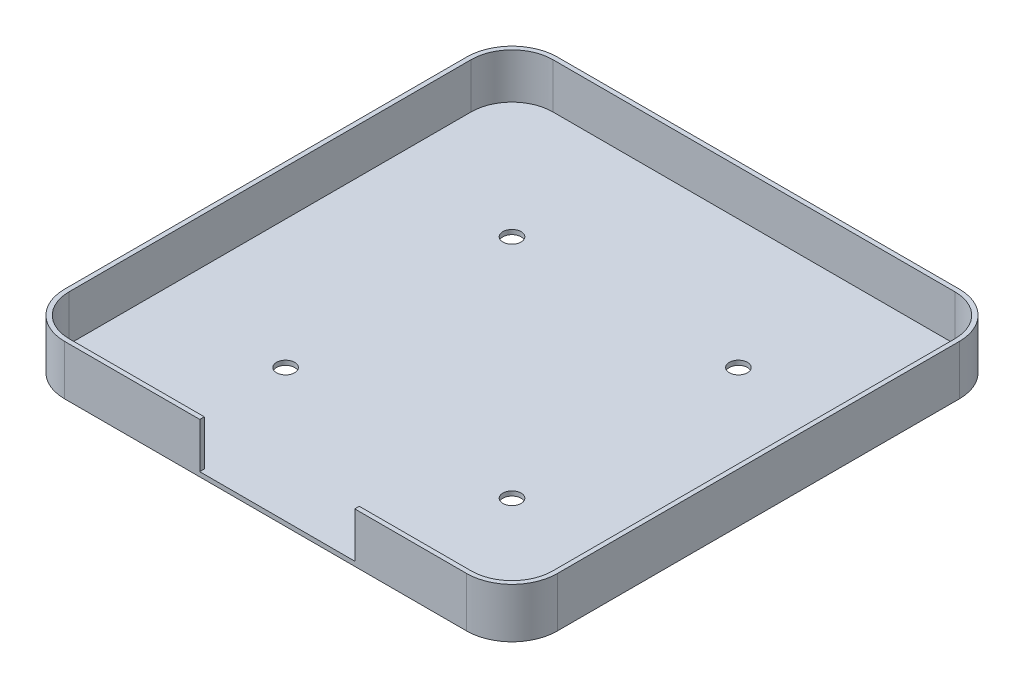
SolidWorks part; units mm, degrees
ref_plane "Front Plane" through (0, 0, 0) normal (0, 0, 1) x (1, 0, 0)
ref_plane "Top Plane" through (0, 0, 0) normal (0, 1, 0) x (1, 0, 0)
ref_plane "Right Plane" through (0, 0, 0) normal (1, 0, 0) x (0, 0, -1)
sketch "Sketch1" plane through (0, 0, 0) normal (0, 1, 0) x (1, 0, 0)
  line L0 (0, 0) -> (29, 0) construction
  line L1 (-25, -29) -> (25, -29)
  line L2 (-29, -25) -> (-29, 25)
  line L3 (-25, 29) -> (25, 29)
  line L4 (29, -25) -> (29, 25)
  line L5 (-29, -29) -> (29, 29) construction
  line L6 (-29, 29) -> (29, -29) construction
  line L7 (-53.4, -44.4) -> (-53.4, 44.4)
  line L8 (-44.4, -54.4) -> (44.4, -54.4)
  line L9 (-54.4, -44.4) -> (-54.4, 44.4)
  line L10 (-44.4, 54.4) -> (44.4, 54.4)
  line L11 (54.4, -44.4) -> (54.4, 44.4)
  line L12 (-54.4, -54.4) -> (54.4, 54.4) construction
  line L13 (-54.4, 54.4) -> (54.4, -54.4) construction
  line L14 (-44.4, 53.4) -> (44.4, 53.4)
  line L15 (53.4, -44.4) -> (53.4, 44.4)
  line L16 (-44.4, -53.4) -> (44.4, -53.4)
  arc A0 (-25, -29) -> (-29, -25) centre (-25, -25) cw
  arc A1 (25, -29) -> (29, -25) centre (25, -25) ccw
  arc A2 (25, 29) -> (29, 25) centre (25, 25) cw
  arc A3 (-29, 25) -> (-25, 29) centre (-25, 25) cw
  circle A4 centre (-25, 25) radius 2
  circle A5 centre (25, 25) radius 2
  circle A6 centre (25, -25) radius 2
  circle A7 centre (-25, -25) radius 2
  arc A8 (44.4, 54.4) -> (54.4, 44.4) centre (44.4, 44.4) cw
  arc A9 (44.4, -54.4) -> (54.4, -44.4) centre (44.4, -44.4) ccw
  arc A10 (-44.4, -54.4) -> (-54.4, -44.4) centre (-44.4, -44.4) cw
  arc A11 (-54.4, 44.4) -> (-44.4, 54.4) centre (-44.4, 44.4) cw
  arc A12 (-53.4, 44.4) -> (-44.4, 53.4) centre (-44.4, 44.4) cw
  arc A13 (44.4, 53.4) -> (53.4, 44.4) centre (44.4, 44.4) cw
  arc A14 (44.4, -53.4) -> (53.4, -44.4) centre (44.4, -44.4) ccw
  arc A15 (-44.4, -53.4) -> (-53.4, -44.4) centre (-44.4, -44.4) cw
  point P0 (0, 0)
  dimension "D3" = 4
  dimension "D4" = 4
  dimension "D5" = 4
  dimension "D8" = 10
  dimension "D1" = 58
  dimension "D2" = 58
  dimension "D6" = 25.4
  dimension "D7" = 25.4
  dimension "D9" = 1
extrude "Boss-Extrude1" add sketch "Sketch1" along normal blind 1 contours A15 L16 A14 L15 A13 L14 A12 L7 L2 A3 L3 A2 L4 A1 L1 A0 | A3 L2 A0 L1 A1 L4 A2 L3 A6 A5 A4 A7 region at (0, 0, 0) region at (-51.8896, 0, 0)
extrude "Boss-Extrude2" add sketch "Sketch1<5>" along normal blind 11 contours A11 L9 A10 L8 A9 L11 A8 L10 L16 A15 L7 A12 L14 A13 L15 A14 region at (-51.3623, 0, 51.3623)
sketch "Sketch1<5>" plane through (0, 0, 0) normal (0, 1, 0) x (1, 0, 0) same geometry as "Sketch1"
sketch "Sketch2" plane through (0, 11, 0) normal (0, 1, 0) x (1, 0, 0)
  line L0 (-53.4, -44.4) -> (-53.4, 44.4) construction
  line L1 (-44.4, -53.4) -> (44.4, -53.4) construction
  line L2 (53.4, -44.4) -> (53.4, 44.4) construction
  line L3 (-44.4, 53.4) -> (44.4, 53.4) construction
  line L4 (-54.4, 44.4) -> (-54.4, -44.4)
  line L5 (-44.4, -54.4) -> (44.4, -54.4)
  line L6 (54.4, -44.4) -> (54.4, 44.4)
  line L7 (44.4, 54.4) -> (-44.4, 54.4)
  line L8 (-54.4, 44.4) -> (-54.4, -44.4)
  line L9 (-44.4, -54.4) -> (44.4, -54.4)
  line L10 (54.4, -44.4) -> (54.4, 44.4)
  line L11 (44.4, 54.4) -> (-44.4, 54.4)
  line L12 (-53.4, -44.4) -> (-53.4, 44.4)
  line L13 (-44.4, -53.4) -> (44.4, -53.4)
  line L14 (53.4, -44.4) -> (53.4, 44.4)
  line L15 (-44.4, 53.4) -> (44.4, 53.4)
  arc A0 (-53.4, -44.4) -> (-44.4, -53.4) centre (-44.4, -44.4) ccw construction
  arc A1 (44.4, -53.4) -> (53.4, -44.4) centre (44.4, -44.4) ccw construction
  arc A2 (53.4, 44.4) -> (44.4, 53.4) centre (44.4, 44.4) ccw construction
  arc A3 (-44.4, 53.4) -> (-53.4, 44.4) centre (-44.4, 44.4) ccw construction
  arc A4 (-44.4, 54.4) -> (-54.4, 44.4) centre (-44.4, 44.4) ccw
  arc A5 (-54.4, -44.4) -> (-44.4, -54.4) centre (-44.4, -44.4) ccw
  arc A6 (44.4, -54.4) -> (54.4, -44.4) centre (44.4, -44.4) ccw
  arc A7 (54.4, 44.4) -> (44.4, 54.4) centre (44.4, 44.4) ccw
  arc A8 (-44.4, 54.4) -> (-54.4, 44.4) centre (-44.4, 44.4) ccw
  arc A9 (-54.4, -44.4) -> (-44.4, -54.4) centre (-44.4, -44.4) ccw
  arc A10 (44.4, -54.4) -> (54.4, -44.4) centre (44.4, -44.4) ccw
  arc A11 (54.4, 44.4) -> (44.4, 54.4) centre (44.4, 44.4) ccw
  arc A12 (-53.4, -44.4) -> (-44.4, -53.4) centre (-44.4, -44.4) ccw
  arc A13 (44.4, -53.4) -> (53.4, -44.4) centre (44.4, -44.4) ccw
  arc A14 (53.4, 44.4) -> (44.4, 53.4) centre (44.4, 44.4) ccw
  arc A15 (-44.4, 53.4) -> (-53.4, 44.4) centre (-44.4, 44.4) ccw
  dimension "D1" = 0
sketch "Sketch3" plane through (0, 0, 54.4) normal (0, 0, -1) x (-1, 0, 0)
  line L1 (-19.6726, 20.0642) -> (14.5574, 20.0642)
  line L2 (-19.6726, 20.0642) -> (-19.6726, 1)
  line L3 (-19.6726, 1) -> (14.5574, 1)
  line L4 (14.5574, 20.0642) -> (14.5574, 1)
  line L8 (-44.4, 0) -> (44.4, 0)
  line L9 (-44.4, 11) -> (-44.4, 0)
  line L10 (44.4, 11) -> (-44.4, 11)
  line L11 (44.4, 0) -> (44.4, 11)
  line L12 (-44.4, 0) -> (44.4, 0)
  line L13 (-44.4, 11) -> (-44.4, 0)
  line L14 (44.4, 11) -> (-44.4, 11)
  line L15 (44.4, 0) -> (44.4, 11)
  line M5 (44.4, 0) -> (-44.4, 0)
  line M7 (-44.4, 11) -> (44.4, 11)
  dimension "D1" = 34.23
  dimension "D3" = 1
  dimension "D2" = 0
extrude "Cut-Extrude2" cut sketch "Sketch3" along normal up to surface (1 mm away) contours L4 L2 M7 M5 region at (2.5576, 6, 54.4) up to face at (0, 6, 53.4)
